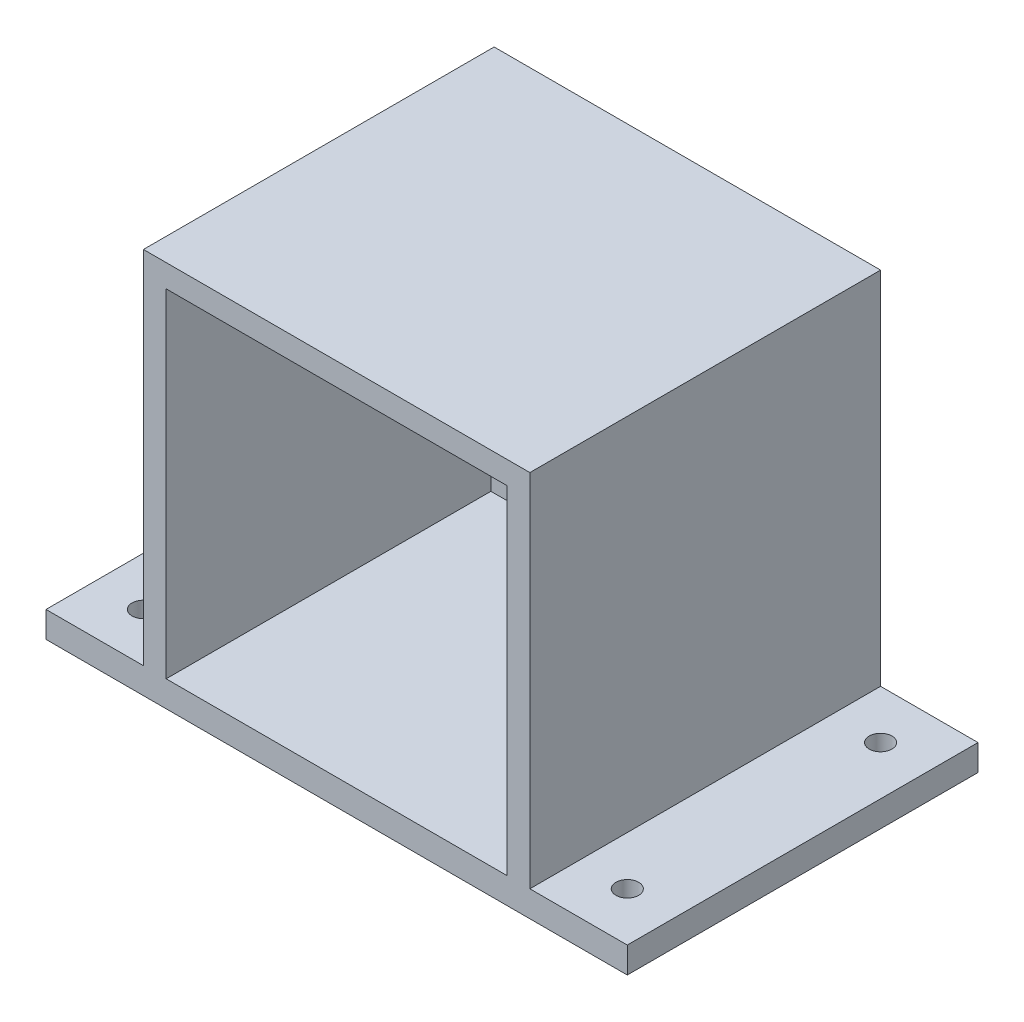
SolidWorks part; units mm, degrees
ref_plane "Front Plane" through (0, 0, 0) normal (0, 0, 1) x (1, 0, 0)
ref_plane "Top Plane" through (0, 0, 0) normal (0, 1, 0) x (1, 0, 0)
ref_plane "Right Plane" through (0, 0, 0) normal (1, 0, 0) x (0, 0, -1)
sketch "Sketch5" plane through (0, 0, 0) normal (0, 0, 1) x (1, 0, 0)
  line L1 (0, 0) -> (52.5, 0)
  line L2 (0, 0) -> (0, 52.5)
  line L3 (0, 52.5) -> (52.5, 52.5)
  line L4 (52.5, 0) -> (52.5, 52.5)
  line L5 (-3.5, 56) -> (56, 56)
  line L6 (-3.5, 56) -> (-3.5, -3.5)
  line L7 (-3.5, -3.5) -> (56, -3.5)
  line L8 (56, 56) -> (56, -3.5)
  dimension "D1" = 52.5
  dimension "D2" = 52.5
  dimension "D3" = 3.5
  dimension "D4" = 3.5
  dimension "D5" = 3.5
  dimension "D6" = 3.5
extrude "Boss-Extrude5" add sketch "Sketch5" along normal blind 54
sketch "Sketch6" plane through (0, 0, 0) normal (0, 0, -1) x (-1, 0, 0)
  line L1 (-56, 56) -> (3.5, 56)
  line L2 (-56, 56) -> (-56, -3.5)
  line L3 (-56, -3.5) -> (3.5, -3.5)
  line L4 (3.5, 56) -> (3.5, -3.5)
extrude "Boss-Extrude6" add sketch "Sketch6" against normal blind 4
sketch "Sketch7" plane through (0, -3.5, 0) normal (0, -1, 0) x (1, 0, 0)
  line L0 (-3.5, 54) -> (-18.5, 54)
  line L1 (-18.5, 54) -> (-18.5, 0)
  line L2 (-18.5, 0) -> (71, 0)
  line L3 (71, 0) -> (71, 54)
  line L4 (71, 54) -> (56, 54)
  line L5 (56, 54) -> (56, 0) construction
  line L6 (-3.5, 54) -> (56, 54) construction
  line L7 (26.25, 0) -> (26.25, 54) construction
  line L8 (-3.5, 54) -> (56, 54)
  circle A0 centre (-11, 46.5) radius 1.75
  circle A1 centre (-11, 7.5) radius 1.75
  circle A2 centre (63.5, 7.5) radius 1.75
  circle A3 centre (63.5, 46.5) radius 1.75
  dimension "D3" = 3.5
  dimension "D6" = 3.5
  dimension "D1" = 15
  dimension "D2" = 15
  dimension "D4" = 7.5
  dimension "D5" = 7.5
  dimension "D7" = 7.5
  dimension "D8" = 7.5
extrude "Boss-Extrude7" add sketch "Sketch7" against normal blind 4
